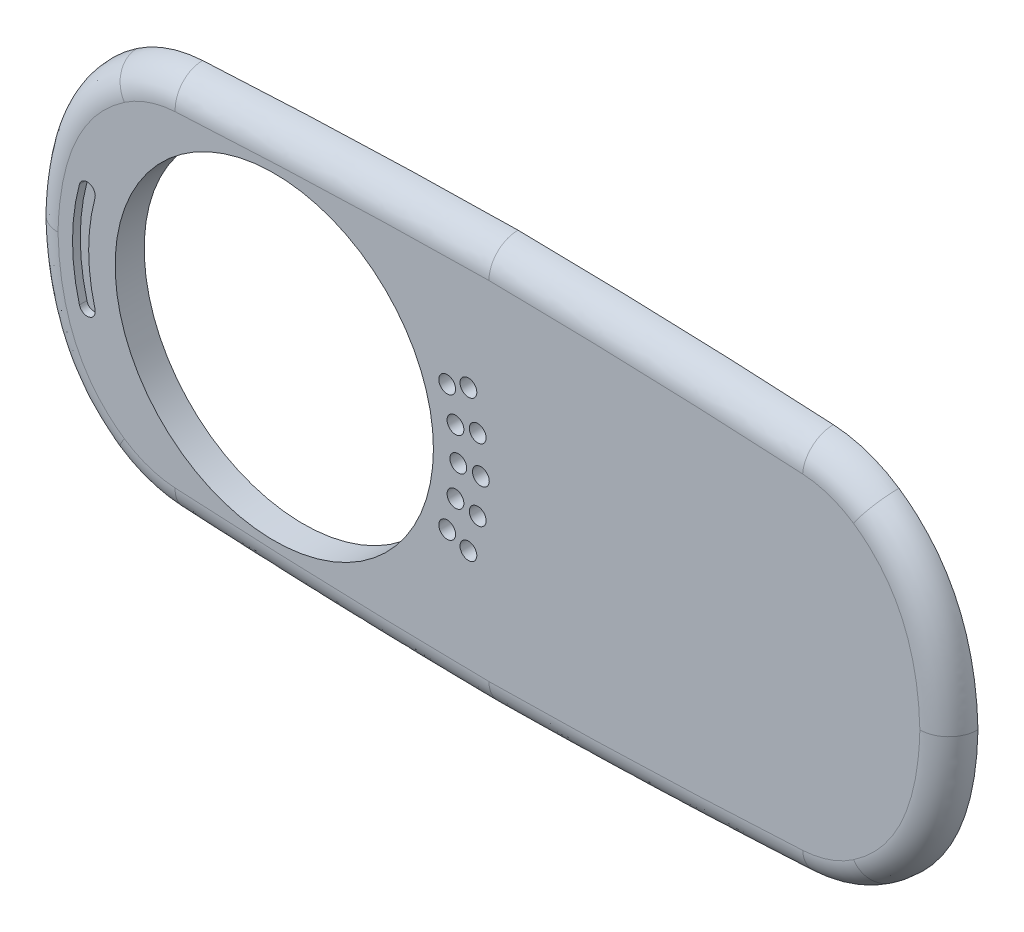
SolidWorks part; units mm, degrees
ref_plane "Front Plane" through (0, 0, 0) normal (0, 0, 1) x (1, 0, 0)
ref_plane "Top Plane" through (0, 0, 0) normal (0, 1, 0) x (1, 0, 0)
ref_plane "Right Plane" through (0, 0, 0) normal (1, 0, 0) x (0, 0, -1)
sketch "Sketch1" plane through (0, 0, 0) normal (0, 0, 1) x (1, 0, 0)
  line L0 (-35.625, 0) -> (35.625, 0) construction
  line L1 (0, 15.7) -> (0, -15.7) construction
  arc A0 (24.4235, -14.8674) -> (29.5009, -13.1395) centre (23.8586, -4.8833) ccw
  arc A1 (24.4235, 14.8674) -> (29.5009, 13.1395) centre (23.8586, 4.8833) cw
  arc A2 (-24.4235, 14.8674) -> (-29.5009, 13.1395) centre (-23.8586, 4.8833) ccw
  arc A3 (-24.4235, -14.8674) -> (-29.5009, -13.1395) centre (-23.8586, -4.8833) cw
  circle A4 centre (-16.625, 0) radius 12.325
  spline S0 degree 3 poles (0, 15.7) (8.1473, 15.6052) (16.2888, 15.3276) (24.4235, 14.8674) knots 0 0 0 0 0.923945 0.923945 0.923945 0.923945
  spline S1 degree 3 poles (29.5009, 13.1395) (29.7988, 12.9359) (33.5991, 10.1134) (35.4967, 5.6063) (35.625, 0) knots 0.189061 0.189061 0.189061 0.189061 0.250305 1 1 1 1
  spline S2 degree 3 poles (0, -15.7) (8.1473, -15.6052) (16.2888, -15.3276) (24.4235, -14.8674) knots 0 0 0 0 0.923945 0.923945 0.923945 0.923945
  spline S3 degree 3 poles (29.5009, -13.1395) (29.7988, -12.9359) (33.5991, -10.1134) (35.4967, -5.6063) (35.625, 0) knots 0.189061 0.189061 0.189061 0.189061 0.250305 1 1 1 1
  spline S4 degree 3 poles (0, 15.7) (-8.1473, 15.6052) (-16.2888, 15.3276) (-24.4235, 14.8674) knots 0 0 0 0 0.923945 0.923945 0.923945 0.923945
  spline S5 degree 3 poles (-29.5009, 13.1395) (-29.7988, 12.9359) (-33.5991, 10.1134) (-35.4967, 5.6063) (-35.625, 0) knots 0.189061 0.189061 0.189061 0.189061 0.250305 1 1 1 1
  spline S6 degree 3 poles (-29.5009, -13.1395) (-29.7988, -12.9359) (-33.5991, -10.1134) (-35.4967, -5.6063) (-35.625, 0) knots 0.189061 0.189061 0.189061 0.189061 0.250305 1 1 1 1
  spline S7 degree 3 poles (0, -15.7) (-8.1473, -15.6052) (-16.2888, -15.3276) (-24.4235, -14.8674) knots 0 0 0 0 0.923945 0.923945 0.923945 0.923945
  dimension "D6" = 10
  dimension "D7" = 24.65
  dimension "D1" = 71.25
  dimension "D2" = 31.4
  dimension "D3" = 15.4
  dimension "D4" = 19
  dimension "D5" = 12.5
extrude "Boss-Extrude1" add sketch "Sketch1" against normal blind 2.25
fillet "Fillet1" radius 2.25 12 edges at (27.0802, 14.3502, 0) (-27.0802, 14.3502, 0) (27.0802, -14.3502, 0) (-27.0802, -14.3502, 0)
sketch "Sketch2" plane through (0, 0, 0) normal (0, 0, 1) x (1, 0, 0)
  line L0 (-16.625, 12.325) -> (-16.625, -12.325) construction
  line L1 (-16.625, 0) -> (-31.625, 0) construction
  line L2 (-16.625, 0) -> (-31.1139, 3.8823) construction
  line L3 (-16.625, 0) -> (-31.1139, -3.8823) construction
  circle A0 centre (-16.625, 0) radius 12.325 construction
  arc A1 (-31.1139, 3.8823) -> (-31.1139, -3.8823) centre (-16.625, 0) ccw construction
  arc A2 (-31.7176, 4.044) -> (-31.7176, -4.044) centre (-16.625, 0) ccw
  arc A3 (-30.5102, 3.7205) -> (-30.5102, -3.7205) centre (-16.625, 0) ccw
  arc A4 (-30.5102, 3.7205) -> (-31.7176, 4.044) centre (-31.1139, 3.8823) ccw
  arc A5 (-31.7176, -4.044) -> (-30.5102, -3.7205) centre (-31.1139, -3.8823) ccw
  dimension "D1" = 15
  dimension "D2" = 15
  dimension "D3" = 0.625
extrude "Cut-Extrude1" cut sketch "Sketch2" against normal blind 1.5
sketch "Sketch3" plane through (0, 0, -1.5) normal (0, 0, 1) x (1, 0, 0)
  arc A0 (-30.6068, 3.7464) -> (-31.621, 4.0182) centre (-31.1139, 3.8823) ccw
  arc A1 (-31.621, 4.0182) -> (-31.621, -4.0182) centre (-16.625, 0) ccw
  arc A2 (-31.621, -4.0182) -> (-30.6068, -3.7464) centre (-31.1139, -3.8823) ccw
  arc A3 (-30.6068, 3.7464) -> (-30.6068, -3.7464) centre (-16.625, 0) ccw
  arc A4 (-30.5102, 3.7205) -> (-31.7176, 4.044) centre (-31.1139, 3.8823) ccw
  arc A5 (-31.7176, 4.044) -> (-31.7176, -4.044) centre (-16.625, 0) ccw
  arc A6 (-31.7176, -4.044) -> (-30.5102, -3.7205) centre (-31.1139, -3.8823) ccw
  arc A7 (-30.5102, 3.7205) -> (-30.5102, -3.7205) centre (-16.625, 0) ccw
  arc A8 (-30.5102, 3.7205) -> (-31.7176, 4.044) centre (-31.1139, 3.8823) ccw construction
  arc A9 (-31.7176, 4.044) -> (-31.7176, -4.044) centre (-16.625, 0) ccw construction
  arc A10 (-31.7176, -4.044) -> (-30.5102, -3.7205) centre (-31.1139, -3.8823) ccw construction
  arc A11 (-30.5102, 3.7205) -> (-30.5102, -3.7205) centre (-16.625, 0) ccw construction
  dimension "D1" = 0
  dimension "D2" = 0.1
extrude "Boss-Extrude3" add sketch "Sketch3" along normal blind 1 separate body
sketch "Sketch4" plane through (0, 0, 0) normal (0, 0, 1) x (1, 0, 0)
  line L0 (-16.625, 0) -> (-2.375, 0) construction
  line L1 (-2.375, 0) -> (-0.625, 0) construction
  line L2 (-16.625, 0) -> (-3.2344, 4.8738) construction
  line L3 (-16.625, 0) -> (-3.2344, -4.8738) construction
  line L4 (-16.625, 0) -> (-0.8681, 2.7784) construction
  line L5 (-16.625, 0) -> (-0.8681, -2.7784) construction
  arc A0 (-3.2344, -4.8738) -> (-3.2344, 4.8738) centre (-16.625, 0) ccw construction
  arc A1 (-1.5899, -5.4723) -> (-1.5899, 5.4723) centre (-16.625, 0) ccw construction
  circle A2 centre (-3.2344, 4.8738) radius 0.65
  circle A3 centre (-2.5915, 2.4745) radius 0.65
  circle A4 centre (-0.8681, 2.7784) radius 0.65
  circle A5 centre (-1.5899, 5.4723) radius 0.65
  circle A6 centre (-2.375, 0) radius 0.65
  circle A7 centre (-0.625, 0) radius 0.65
  circle A8 centre (-1.5899, -5.4723) radius 0.65
  circle A9 centre (-3.2344, -4.8738) radius 0.65
  circle A10 centre (-0.8681, -2.7784) radius 0.65
  circle A11 centre (-2.5915, -2.4745) radius 0.65
  dimension "D6" = 1.3
  dimension "D1" = 14.25
  dimension "D2" = 16
  dimension "D3" = 20
  dimension "D5" = 10
  dimension "D4" = 1.75
extrude "Cut-Extrude2" cut sketch "Sketch4" against normal up to surface (2.25 mm away) up to face at (-4.3, 0, -2.25)
